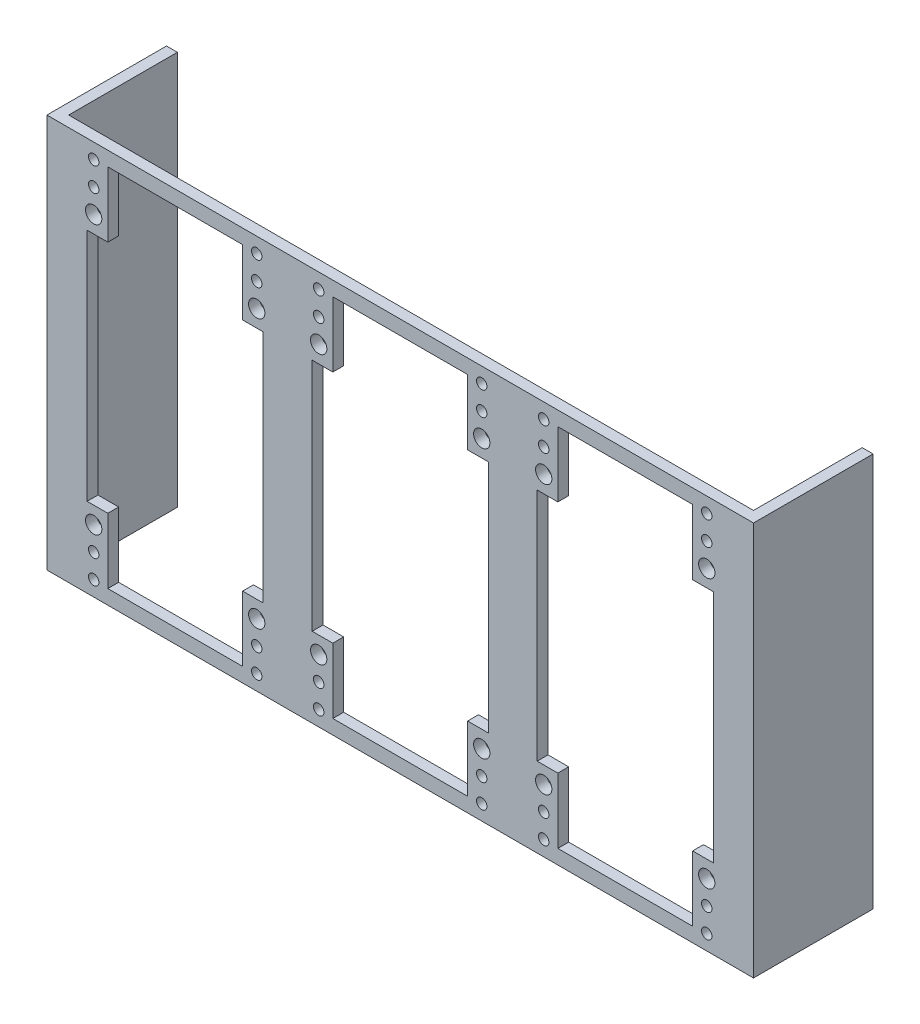
SolidWorks part; units mm, degrees
ref_plane "Front Plane" through (0, 0, 0) normal (0, 0, 1) x (1, 0, 0)
ref_plane "Top Plane" through (0, 0, 0) normal (0, 1, 0) x (1, 0, 0)
ref_plane "Right Plane" through (0, 0, 0) normal (1, 0, 0) x (0, 0, -1)
sketch "Sketch1" plane through (0, 0, 0) normal (0, 0, 1) x (1, 0, 0)
  line L8 (177.1103, 119.2472) -> (342.2103, 119.2472)
  line L9 (177.1103, 119.2472) -> (177.1103, 27.1722)
  line L10 (177.1103, 27.1722) -> (342.2103, 27.1722)
  line L11 (342.2103, 119.2472) -> (342.2103, 27.1722)
  dimension "D1" = 165.1
  dimension "D2" = 92.075
extrude "Boss-Extrude1" add sketch "Sketch1" against normal blind 2.54 contours L9 L10 L11 region at (259.6603, 73.2097, 0)
sketch "Sketch2" plane through (0, 0, 0) normal (0, 0, 1) x (1, 0, 0)
  line L0 (227.6563, 73.2097) -> (239.0863, 73.2097) construction
  line L1 (280.2343, 73.2097) -> (291.6643, 73.2097) construction
  line L2 (186.5083, 73.2097) -> (177.1103, 73.2097) construction
  line L3 (177.1103, 119.2472) -> (177.1103, 27.1722) construction
  line L4 (332.8123, 64.776) -> (342.2103, 64.776) construction
  line L5 (342.2103, 119.2472) -> (342.2103, 27.1722) construction
  line L6 (212.904, 115.8817) -> (212.904, 119.2472) construction
  line L8 (177.1103, 119.2472) -> (342.2103, 119.2472) construction
  line L11 (207.0823, 30.5377) -> (207.0823, 27.1722) construction
  line L12 (177.1103, 27.1722) -> (342.2103, 27.1722) construction
  line B0 (191.3343, 115.8817) -> (222.8303, 115.8817)
  line B1 (191.3343, 115.8817) -> (191.3343, 100.6417)
  line B2 (191.3343, 100.6417) -> (186.5083, 100.6417)
  line B3 (186.5083, 100.6417) -> (186.5083, 45.7777)
  line B4 (186.5083, 45.7777) -> (191.3343, 45.7777)
  line B5 (191.3343, 45.7777) -> (191.3343, 30.5377)
  line B6 (191.3343, 30.5377) -> (222.8303, 30.5377)
  line B7 (222.8303, 30.5377) -> (222.8303, 45.7777)
  line B8 (222.8303, 45.7777) -> (227.6563, 45.7777)
  line B9 (227.6563, 45.7777) -> (227.6563, 100.6417)
  line B10 (227.6563, 100.6417) -> (222.8303, 100.6417)
  line B11 (222.8303, 100.6417) -> (222.8303, 115.8817)
  circle B12 centre (188.0323, 41.8153) radius 1.905
  circle B13 centre (226.1323, 104.6041) radius 1.905
  circle B14 centre (188.0323, 104.6041) radius 1.905
  circle B15 centre (188.0323, 36.2781) radius 1.2192
  circle B16 centre (188.0323, 30.7155) radius 1.2192
  circle B17 centre (226.1323, 41.8153) radius 1.905
  circle B18 centre (226.1323, 36.2781) radius 1.2192
  circle B19 centre (226.1323, 30.7155) radius 1.2192
  circle B20 centre (226.1323, 110.1413) radius 1.2192
  circle B21 centre (226.1323, 115.7039) radius 1.2192
  circle B22 centre (188.0323, 110.1413) radius 1.2192
  circle B23 centre (188.0323, 115.7039) radius 1.2192
  line B24 (243.9123, 115.8817) -> (275.4083, 115.8817)
  line B25 (243.9123, 115.8817) -> (243.9123, 100.6417)
  line B26 (243.9123, 100.6417) -> (239.0863, 100.6417)
  line B27 (239.0863, 100.6417) -> (239.0863, 45.7777)
  line B28 (239.0863, 45.7777) -> (243.9123, 45.7777)
  line B29 (243.9123, 45.7777) -> (243.9123, 30.5377)
  line B30 (243.9123, 30.5377) -> (275.4083, 30.5377)
  line B31 (275.4083, 30.5377) -> (275.4083, 45.7777)
  line B32 (275.4083, 45.7777) -> (280.2343, 45.7777)
  line B33 (280.2343, 45.7777) -> (280.2343, 100.6417)
  line B34 (280.2343, 100.6417) -> (275.4083, 100.6417)
  line B35 (275.4083, 100.6417) -> (275.4083, 115.8817)
  circle B36 centre (240.6103, 41.8153) radius 1.905
  circle B37 centre (278.7103, 104.6041) radius 1.905
  circle B38 centre (240.6103, 104.6041) radius 1.905
  circle B39 centre (240.6103, 36.2781) radius 1.2192
  circle B40 centre (240.6103, 30.7155) radius 1.2192
  circle B41 centre (278.7103, 41.8153) radius 1.905
  circle B42 centre (278.7103, 36.2781) radius 1.2192
  circle B43 centre (278.7103, 30.7155) radius 1.2192
  circle B44 centre (278.7103, 110.1413) radius 1.2192
  circle B45 centre (278.7103, 115.7039) radius 1.2192
  circle B46 centre (240.6103, 110.1413) radius 1.2192
  circle B47 centre (240.6103, 115.7039) radius 1.2192
  line B48 (296.4903, 115.8817) -> (327.9863, 115.8817)
  line B49 (296.4903, 115.8817) -> (296.4903, 100.6417)
  line B50 (296.4903, 100.6417) -> (291.6643, 100.6417)
  line B51 (291.6643, 100.6417) -> (291.6643, 45.7777)
  line B52 (291.6643, 45.7777) -> (296.4903, 45.7777)
  line B53 (296.4903, 45.7777) -> (296.4903, 30.5377)
  line B54 (296.4903, 30.5377) -> (327.9863, 30.5377)
  line B55 (327.9863, 30.5377) -> (327.9863, 45.7777)
  line B56 (327.9863, 45.7777) -> (332.8123, 45.7777)
  line B57 (332.8123, 45.7777) -> (332.8123, 100.6417)
  line B58 (332.8123, 100.6417) -> (327.9863, 100.6417)
  line B59 (327.9863, 100.6417) -> (327.9863, 115.8817)
  circle B60 centre (293.1883, 41.8153) radius 1.905
  circle B61 centre (331.2883, 104.6041) radius 1.905
  circle B62 centre (293.1883, 104.6041) radius 1.905
  circle B63 centre (293.1883, 36.2781) radius 1.2192
  circle B64 centre (293.1883, 30.7155) radius 1.2192
  circle B65 centre (331.2883, 41.8153) radius 1.905
  circle B66 centre (331.2883, 36.2781) radius 1.2192
  circle B67 centre (331.2883, 30.7155) radius 1.2192
  circle B68 centre (331.2883, 110.1413) radius 1.2192
  circle B69 centre (331.2883, 115.7039) radius 1.2192
  circle B70 centre (293.1883, 110.1413) radius 1.2192
  circle B71 centre (293.1883, 115.7039) radius 1.2192
  dimension "D1" = 11.43
sketch_block_instance "Button Panel-1"
sketch_block "Button Panel" parameters "D7"=2.4384, "D14"=3.81, "D1"=85.344, "D2"=31.496, "D3"=38.1, "D4"=62.7888, "D5"=5.5372, "D6"=5.5626, "D8"=5.5372, "D9"=5.5626, "D10"=5.5372, "D11"=5.5372, "D12"=4.826, "D13"=3.302, "D15"=5.5626
sketch_block_instance "Button Panel-3"
sketch_block_instance "Button Panel-4" parameters "D1"=7.5946, "D2"=196.9279
extrude "Cut-Extrude1" cut sketch "Sketch2" against normal blind 2.54
sketch "Sketch4" plane through (0, 0, -2.54) normal (0, 0, -1) x (-1, 0, 0)
  line L0 (-177.1103, 27.1722) -> (-342.2103, 27.1722) construction
  line L1 (-342.2103, 119.2472) -> (-339.6703, 119.2472)
  line L2 (-342.2103, 119.2472) -> (-342.2103, 27.1722)
  line L3 (-342.2103, 27.1722) -> (-339.6703, 27.1722)
  line L4 (-339.6703, 119.2472) -> (-339.6703, 27.1722)
  line L6 (-177.1103, 119.2472) -> (-179.6503, 119.2472)
  line L7 (-177.1103, 119.2472) -> (-177.1103, 27.1722)
  line L8 (-177.1103, 27.1722) -> (-179.6503, 27.1722)
  line L9 (-179.6503, 119.2472) -> (-179.6503, 27.1722)
  dimension "D1" = 2.54
extrude "Boss-Extrude3" add sketch "Sketch4" along normal blind 25.4
